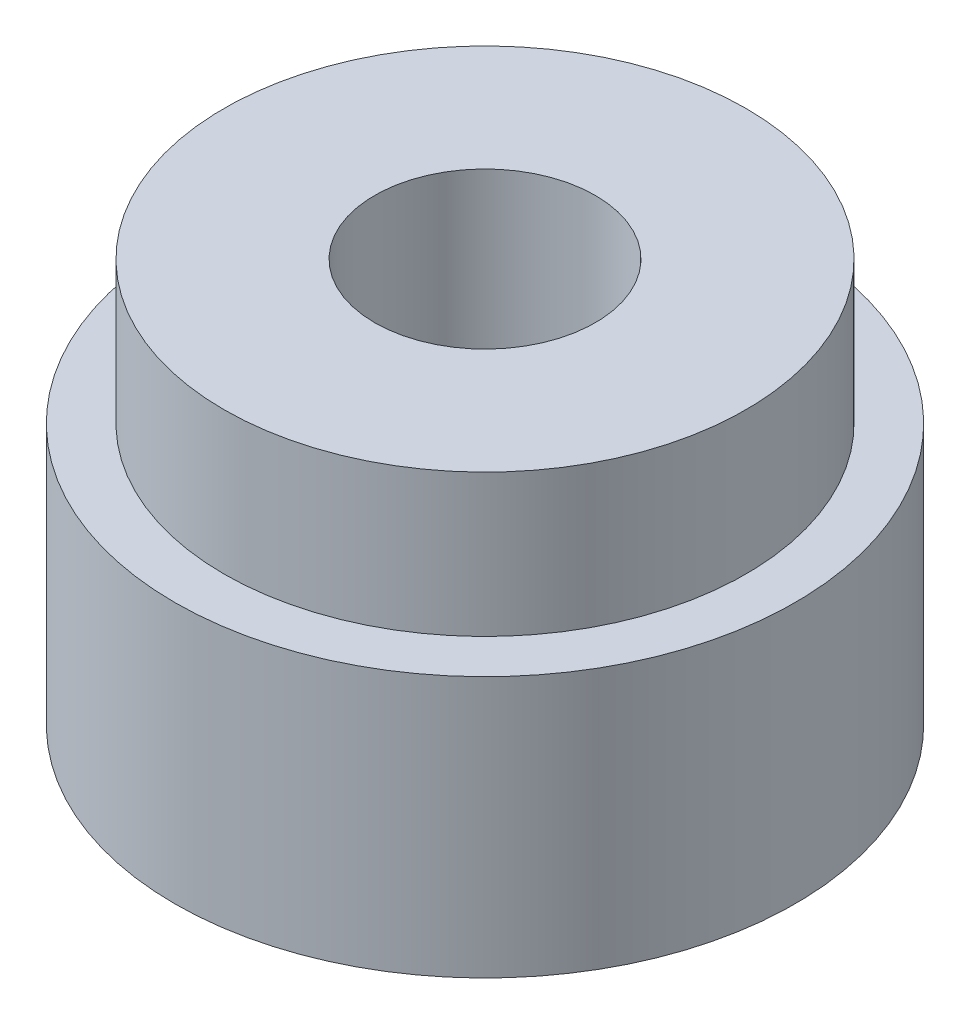
SolidWorks part; units mm, degrees
ref_plane "Front Plane" through (0, 0, 0) normal (0, 0, 1) x (1, 0, 0)
ref_plane "Top Plane" through (0, 0, 0) normal (0, 1, 0) x (1, 0, 0)
ref_plane "Right Plane" through (0, 0, 0) normal (1, 0, 0) x (0, 0, -1)
sketch "Sketch1" plane through (0, 0, 0) normal (0, 1, 0) x (1, 0, 0)
  circle A0 centre (0, 0) radius 11
  circle A1 centre (0, 0) radius 13.075
  circle A2 centre (0, 0) radius 4.65
  dimension "D1" = 22
  dimension "D2" = 26.15
  dimension "D3" = 9.3
extrude "Boss-Extrude1" add sketch "Sketch1" along normal blind 17 contours A0 A2 region at (-10.6889, 0, 0)
extrude "Boss-Extrude2" add sketch "Sketch1<5>" along normal blind 11 contours A1 A0 region at (-12.7052, 0, 0)
sketch "Sketch1<5>" plane through (0, 0, 0) normal (0, 1, 0) x (1, 0, 0) same geometry as "Sketch1"
sketch "Sketch2" plane through (0, 0, 0) normal (0, -1, 0) x (1, 0, 0)
  circle A0 centre (0, 0) radius 9
  dimension "D1" = 18
extrude "Cut-Extrude1" cut sketch "Sketch2" against normal blind 9.15
